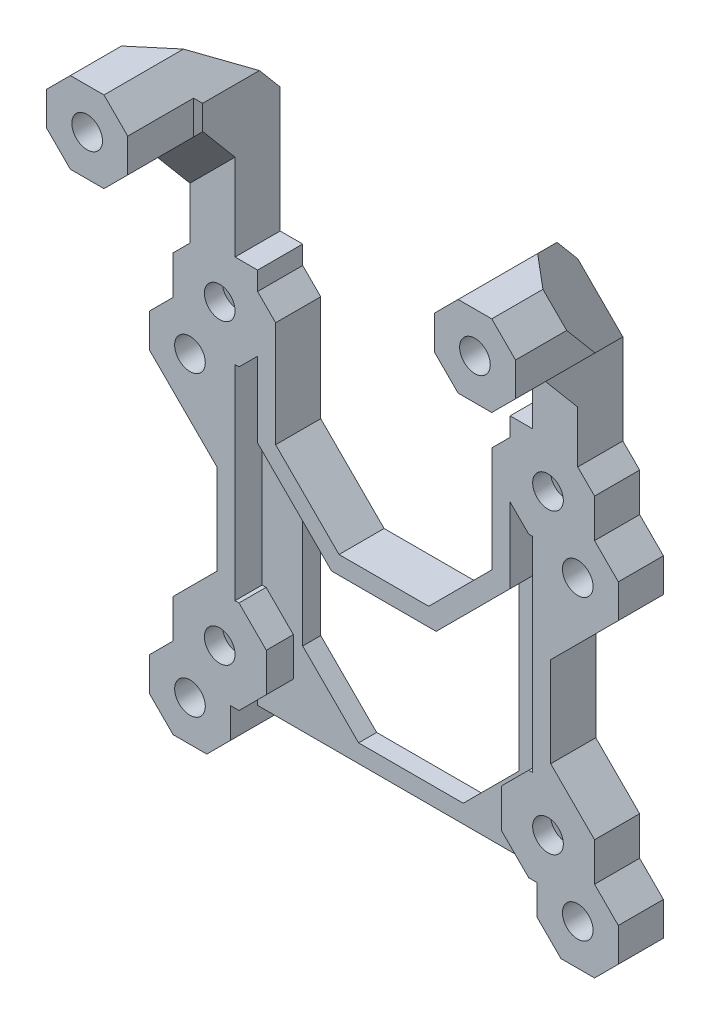
SolidWorks part; units mm, degrees
ref_plane "Front Plane" through (0, 0, 0) normal (0, 0, 1) x (1, 0, 0)
ref_plane "Top Plane" through (0, 0, 0) normal (0, 1, 0) x (1, 0, 0)
ref_plane "Right Plane" through (0, 0, 0) normal (1, 0, 0) x (0, 0, -1)
sketch "Sketch1" plane through (0, 0, 0) normal (0, 0, 1) x (1, 0, 0)
  line L0 (-21.5, 0) -> (21.5, 0) construction
  line L1 (21.5, 0) -> (21.5, 60) construction
  line L2 (21.5, 60) -> (-21.5, 60) construction
  line L3 (-21.5, 60) -> (-21.5, 0) construction
  line L4 (-21.5, 33) -> (21.5, 33) construction
  line L5 (0, 0) -> (0, 60) construction
  line L9 (-5.799, 20) -> (0, 20)
  line L12 (0, 60) -> (0, 76.4523) construction
  line L15 (-16.5, 34.364) -> (-16.5, 60) construction
  line L16 (-20.339, 11.8029) -> (-18.5, 13.6419)
  line L17 (-16.061, 11.8029) -> (-20.339, 11.8029)
  line L18 (-20.339, 11.8029) -> (-23.364, 8.778)
  line L19 (-23.364, 8.778) -> (-23.364, 4.5)
  line L20 (-23.364, 4.5) -> (-20.339, 1.475)
  line L21 (-20.339, 1.475) -> (-16.061, 1.475)
  line L23 (-13.036, 37.5) -> (-13.036, 41.778)
  line L24 (-13.036, 41.778) -> (-16.061, 44.8029)
  line L25 (-16.061, 44.8029) -> (-20.339, 44.8029)
  line L26 (-20.339, 44.8029) -> (-23.364, 41.778)
  line L27 (-23.364, 41.778) -> (-23.364, 37.5)
  line L28 (-23.364, 37.5) -> (-20.339, 34.475)
  line L29 (-20.339, 34.475) -> (-16.061, 34.475)
  line L30 (-16.061, 34.475) -> (-13.036, 37.5)
  line L31 (13.036, 37.5) -> (16.061, 34.475)
  line L32 (16.061, 34.475) -> (20.339, 34.475)
  line L33 (20.339, 34.475) -> (23.364, 37.5)
  line L34 (23.364, 37.5) -> (23.364, 41.778)
  line L35 (23.364, 41.778) -> (20.339, 44.8029)
  line L36 (20.339, 44.8029) -> (16.061, 44.8029)
  line L37 (16.061, 44.8029) -> (13.036, 41.778)
  line L38 (13.036, 41.778) -> (13.036, 37.5)
  line L39 (-14, 0) -> (-14, 51.1419) construction
  line L40 (-16.5, 0) -> (-16.5, 33) construction
  line L41 (-17, 58.136) -> (-17, 61.864)
  line L42 (-17, 61.864) -> (-19.636, 64.5)
  line L43 (-19.636, 64.5) -> (-23.364, 64.5)
  line L44 (-23.364, 64.5) -> (-26, 61.864)
  line L45 (-26, 61.864) -> (-26, 58.136)
  line L46 (-26, 58.136) -> (-23.364, 55.5)
  line L47 (-23.364, 55.5) -> (-19.636, 55.5)
  line L48 (-19.636, 55.5) -> (-17, 58.136)
  line L49 (-23.364, 37.5) -> (-26, 34.864)
  line L50 (-26, 34.864) -> (-26, 31.136)
  line L51 (-26, 31.136) -> (-23.364, 28.5)
  line L52 (-23.364, 28.5) -> (-19.636, 28.5)
  line L53 (-19.636, 28.5) -> (-17, 31.136)
  line L54 (-17, 31.136) -> (-17, 34.864)
  line L55 (-17, 34.864) -> (-19.636, 37.5)
  line L56 (-19.636, 37.5) -> (-23.364, 37.5)
  line L57 (-23.364, 4.5) -> (-26, 1.864)
  line L58 (-26, 1.864) -> (-26, -1.864)
  line L59 (-26, -1.864) -> (-23.364, -4.5)
  line L60 (-23.364, -4.5) -> (-19.636, -4.5)
  line L61 (-19.636, -4.5) -> (-17, -1.864)
  line L62 (-17, -1.864) -> (-17, 1.864)
  line L63 (-17, 1.864) -> (-19.636, 4.5)
  line L64 (-19.636, 4.5) -> (-23.364, 4.5)
  line L65 (23.364, -4.5) -> (26, -1.864)
  line L66 (26, -1.864) -> (26, 1.864)
  line L67 (26, 1.864) -> (23.364, 4.5)
  line L68 (23.364, 4.5) -> (19.636, 4.5)
  line L69 (19.636, 4.5) -> (17, 1.864)
  line L70 (17, 1.864) -> (17, -1.864)
  line L71 (17, -1.864) -> (19.636, -4.5)
  line L72 (19.636, -4.5) -> (23.364, -4.5)
  line L73 (19.636, 28.5) -> (23.364, 28.5)
  line L74 (23.364, 28.5) -> (26, 31.136)
  line L75 (26, 31.136) -> (26, 34.864)
  line L76 (26, 34.864) -> (23.364, 37.5)
  line L77 (23.364, 37.5) -> (19.636, 37.5)
  line L78 (19.636, 37.5) -> (17, 34.864)
  line L79 (17, 34.864) -> (17, 31.136)
  line L80 (17, 31.136) -> (19.636, 28.5)
  line L81 (23.364, 64.5) -> (19.636, 64.5)
  line L82 (19.636, 64.5) -> (17, 61.864)
  line L83 (17, 61.864) -> (17, 58.136)
  line L84 (17, 58.136) -> (19.636, 55.5)
  line L85 (19.636, 55.5) -> (23.364, 55.5)
  line L86 (23.364, 55.5) -> (26, 58.136)
  line L87 (26, 58.136) -> (26, 61.864)
  line L88 (26, 61.864) -> (23.364, 64.5)
  line L89 (-12, 34) -> (-12, 68.1911) construction
  line L90 (12, 34) -> (12, 71.0139) construction
  line L95 (-16.5, 0) -> (-16.5, 34.364)
  line L100 (-4.9706, 22) -> (0, 22)
  line L101 (0, 0) -> (-16.5, 0) construction
  line L103 (-12, 40.7419) -> (-12, 29.0294)
  line L106 (-23.364, 55.5) -> (-21.5, 53.636)
  line L107 (-23.364, 37.5) -> (-21.5, 39.364)
  line L108 (-21.5, 39.364) -> (-21.5, 53.636)
  line L109 (-23.364, 4.5) -> (-18.5, 9.364)
  line L110 (-18.5, 9.364) -> (-18.5, 23.636)
  line L111 (-18.5, 23.636) -> (-23.364, 28.5)
  line L117 (-14, 42.7419) -> (-14, 28.201)
  line L119 (-17, 34.864) -> (-16.5, 34.364)
  line L120 (-19.636, 37.5) -> (-19.5, 37.364)
  line L121 (-19.5, 37.364) -> (-19.5, 55.636)
  line L122 (-19.5, 55.636) -> (-19.636, 55.5)
  line L124 (-19.636, 55.5) -> (-19.5, 55.636)
  line L126 (-16.061, 1.475) -> (-13.036, 4.5)
  line L131 (-4.9706, 22) -> (-12, 29.0294)
  line L132 (-12, 26.201) -> (-12, 8.201)
  line L134 (-12, 26.201) -> (-5.799, 20)
  line L135 (-12, 26.201) -> (-14, 28.201)
  line L136 (-13.036, 4.5) -> (-13.036, 8.778)
  line L137 (-13.036, 8.778) -> (-16.061, 11.8029)
  line L138 (0, 0) -> (-17, 0)
  line L139 (-17, 0) -> (0, 0)
  line L140 (0, 2) -> (-5.799, 2)
  line L141 (-5.799, 2) -> (-12, 8.201)
  line L142 (-13.036, 41.778) -> (-12, 40.7419)
  line L143 (-17, 61.864) -> (-16.5, 61.364)
  line L144 (-16.061, 44.8029) -> (-16.5, 45.2419)
  line L145 (-16.5, 45.2419) -> (-16.5, 61.364)
  line L146 (-16.061, 44.8029) -> (-12, 44.8029)
  line L147 (-16.4968, 42.589) -> (-19.9032, 42.589)
  line L148 (-19.9032, 42.589) -> (-21.6064, 39.639)
  line L149 (-21.6064, 39.639) -> (-19.9032, 36.689)
  line L150 (-19.9032, 36.689) -> (-16.4968, 36.689)
  line L151 (-16.4968, 36.689) -> (-14.7936, 39.639)
  line L152 (-14.7936, 39.639) -> (-16.4968, 42.589)
  line L153 (-16.4968, 9.589) -> (-19.9032, 9.589)
  line L154 (-19.9032, 9.589) -> (-21.6064, 6.639)
  line L155 (-21.6064, 6.639) -> (-19.9032, 3.689)
  line L156 (-19.9032, 3.689) -> (-16.4968, 3.689)
  line L157 (-16.4968, 3.689) -> (-14.7936, 6.639)
  line L158 (-14.7936, 6.639) -> (-16.4968, 9.589)
  line L159 (-12, 44.8029) -> (-12, 40.7419)
  circle A0 centre (-21.5, 60) radius 1.7
  circle A1 centre (-21.5, 33) radius 1.7
  circle A2 centre (-21.5, 0) radius 1.7
  circle A3 centre (21.5, 0) radius 1.7
  circle A4 centre (21.5, 33) radius 1.7
  circle A5 centre (21.5, 60) radius 1.7
  circle A7 centre (-18.2, 6.639) radius 1.7
  circle A8 centre (-18.2, 39.639) radius 1.7
  circle A9 centre (18.2, 39.639) radius 1.7
  circle A10 centre (0, 34) radius 12 construction
  circle A11 centre (0, 56) radius 12 construction
  circle A13 centre (-18.2, 39.639) radius 5.164 construction
  circle A14 centre (18.2, 39.639) radius 5.164 construction
  circle A15 centre (-21.5, 60) radius 4.5 construction
  circle A16 centre (-21.5, 33) radius 4.5 construction
  circle A17 centre (-21.5, 0) radius 4.5 construction
  circle A18 centre (21.5, 0) radius 4.5 construction
  circle A19 centre (21.5, 33) radius 4.5 construction
  circle A20 centre (21.5, 60) radius 4.5 construction
  circle A22 centre (-18.2, 6.639) radius 5.164 construction
  circle A23 centre (-18.2, 39.639) radius 2.95 construction
  circle A24 centre (-18.2, 6.639) radius 2.95 construction
  dimension "D4" = 3.4
  dimension "D5" = 24
  dimension "D7" = 2
  dimension "D8" = 5.9
  dimension "D9" = 9
  dimension "D10" = 9
  dimension "D11" = 9
  dimension "D12" = 9
  dimension "D13" = 9
  dimension "D14" = 9
  dimension "D6" = 2
  dimension "D1" = 43
  dimension "D2" = 33
  dimension "D3" = 27
  dimension "D15" = 2.5
  dimension "D16" = 2
  dimension "D17" = 2
  dimension "D19" = 135
  dimension "D22" = 2
  dimension "D23" = 2
  dimension "D24" = 34
  dimension "D25" = 2
  dimension "D26" = 22
sketch "Sketch5" plane through (0, 0, 0) normal (0, 0, 1) x (1, 0, 0)
  line L0 (16.5, 44.8029) -> (16.5, 45.2419)
  line L1 (16.061, 44.8029) -> (16.5, 44.8029)
  line L12 (0, 0) -> (0, 60) construction
  line L13 (0, 2) -> (-5.799, 2) construction
  line L14 (-5.799, 2) -> (-12, 8.201) construction
  line L15 (-12, 26.201) -> (-12, 8.201) construction
  line L16 (-12, 26.201) -> (-5.799, 20) construction
  line L17 (-5.799, 20) -> (0, 20) construction
  line L18 (-4.9706, 22) -> (0, 22) construction
  line L19 (-4.9706, 22) -> (-12, 29.0294) construction
  line L20 (-12, 40.7419) -> (-12, 29.0294) construction
  line L21 (-13.036, 41.778) -> (-12, 40.7419) construction
  line L22 (-13.036, 41.778) -> (-16.061, 44.8029) construction
  line L24 (-16.5, 45.2419) -> (-16.5, 61.364) construction
  line L25 (-17, 61.864) -> (-16.5, 61.364) construction
  line L26 (-17, 61.864) -> (-19.636, 64.5) construction
  line L27 (-19.636, 64.5) -> (-23.364, 64.5) construction
  line L28 (-23.364, 64.5) -> (-26, 61.864) construction
  line L29 (-26, 61.864) -> (-26, 58.136) construction
  line L30 (-26, 58.136) -> (-23.364, 55.5) construction
  line L31 (-23.364, 55.5) -> (-21.5, 53.636) construction
  line L32 (-21.5, 39.364) -> (-21.5, 53.636) construction
  line L33 (-20.339, 44.8029) -> (-23.364, 41.778) construction
  line L34 (-23.364, 41.778) -> (-23.364, 37.5) construction
  line L35 (-23.364, 37.5) -> (-26, 34.864) construction
  line L36 (-26, 34.864) -> (-26, 31.136) construction
  line L37 (-26, 31.136) -> (-23.364, 28.5) construction
  line L38 (-18.5, 23.636) -> (-23.364, 28.5) construction
  line L39 (-18.5, 9.364) -> (-18.5, 23.636) construction
  line L40 (-20.339, 11.8029) -> (-18.5, 13.6419) construction
  line L41 (-20.339, 11.8029) -> (-23.364, 8.778) construction
  line L42 (-23.364, 8.778) -> (-23.364, 4.5) construction
  line L43 (-23.364, 4.5) -> (-26, 1.864) construction
  line L44 (-26, 1.864) -> (-26, -1.864) construction
  line L45 (-26, -1.864) -> (-23.364, -4.5) construction
  line L46 (-23.364, -4.5) -> (-19.636, -4.5) construction
  line L47 (-19.636, -4.5) -> (-17, -1.864) construction
  line L48 (-17, -1.864) -> (-17, 1.864) construction
  line L49 (0, 0) -> (-17, 0) construction
  line L50 (0, 0) -> (0, 60) construction
  line L51 (5.799, 2) -> (-5.799, 2)
  line L52 (-5.799, 2) -> (-12, 8.201)
  line L53 (-12, 26.201) -> (-12, 8.201)
  line L54 (-12, 26.201) -> (-5.799, 20)
  line L55 (-5.799, 20) -> (5.799, 20)
  line L56 (-4.9706, 22) -> (4.9706, 22)
  line L57 (-4.9706, 22) -> (-12, 29.0294)
  line L58 (-12, 40.7419) -> (-12, 29.0294)
  line L59 (-13.036, 41.778) -> (-12, 40.7419)
  line L60 (-13.036, 41.778) -> (-14, 42.7419)
  line L62 (-16.5, 60) -> (-16.5, 61.364)
  line L63 (-17, 61.864) -> (-16.5, 61.364)
  line L64 (-17, 61.864) -> (-19.636, 64.5)
  line L65 (-19.636, 64.5) -> (-23.364, 64.5)
  line L66 (-23.364, 64.5) -> (-26, 61.864)
  line L67 (-26, 61.864) -> (-26, 58.136)
  line L68 (-26, 58.136) -> (-23.364, 55.5)
  line L69 (-23.364, 55.5) -> (-21.5, 53.636)
  line L70 (-21.5, 43.6419) -> (-21.5, 53.636)
  line L71 (-21.5, 43.6419) -> (-23.364, 41.778)
  line L72 (-23.364, 41.778) -> (-23.364, 37.5)
  line L73 (-23.364, 37.5) -> (-26, 34.864)
  line L74 (-26, 34.864) -> (-26, 31.136)
  line L75 (-26, 31.136) -> (-23.364, 28.5)
  line L76 (-18.5, 23.636) -> (-23.364, 28.5)
  line L77 (-18.5, 13.6419) -> (-18.5, 23.636)
  line L78 (-20.339, 11.8029) -> (-18.5, 13.6419)
  line L79 (-20.339, 11.8029) -> (-23.364, 8.778)
  line L80 (-23.364, 8.778) -> (-23.364, 4.5)
  line L81 (-23.364, 4.5) -> (-26, 1.864)
  line L82 (-26, 1.864) -> (-26, -1.864)
  line L83 (-26, -1.864) -> (-23.364, -4.5)
  line L84 (-23.364, -4.5) -> (-19.636, -4.5)
  line L85 (-19.636, -4.5) -> (-17, -1.864)
  line L86 (-17, -1.864) -> (-17, 0)
  line L87 (17, 0) -> (-17, 0)
  line L88 (17, -1.864) -> (17, 0)
  line L89 (19.636, -4.5) -> (17, -1.864)
  line L90 (23.364, -4.5) -> (19.636, -4.5)
  line L91 (26, -1.864) -> (23.364, -4.5)
  line L92 (26, 1.864) -> (26, -1.864)
  line L93 (23.364, 4.5) -> (26, 1.864)
  line L94 (23.364, 8.778) -> (23.364, 4.5)
  line L95 (20.339, 11.8029) -> (23.364, 8.778)
  line L96 (20.339, 11.8029) -> (18.5, 13.6419)
  line L97 (18.5, 13.6419) -> (18.5, 23.636)
  line L98 (18.5, 23.636) -> (23.364, 28.5)
  line L99 (26, 31.136) -> (23.364, 28.5)
  line L100 (26, 34.864) -> (26, 31.136)
  line L101 (23.364, 37.5) -> (26, 34.864)
  line L139 (23.364, 41.778) -> (23.364, 37.5)
  line L140 (21.5, 43.6419) -> (23.364, 41.778)
  line L141 (21.5, 43.6419) -> (21.5, 53.636)
  line L142 (23.364, 55.5) -> (21.5, 53.636)
  line L143 (26, 58.136) -> (23.364, 55.5)
  line L144 (26, 61.864) -> (26, 58.136)
  line L145 (23.364, 64.5) -> (26, 61.864)
  line L146 (19.636, 64.5) -> (23.364, 64.5)
  line L147 (17, 61.864) -> (19.636, 64.5)
  line L148 (17, 61.864) -> (16.5, 61.364)
  line L149 (16.5, 45.2419) -> (16.5, 61.364)
  line L151 (13.036, 41.778) -> (14, 42.7419)
  line L152 (13.036, 41.778) -> (12, 40.7419)
  line L153 (12, 40.7419) -> (12, 29.0294)
  line L154 (4.9706, 22) -> (12, 29.0294)
  line L155 (12, 26.201) -> (5.799, 20)
  line L156 (12, 26.201) -> (12, 8.201)
  line L157 (5.799, 2) -> (12, 8.201)
  line L158 (-16.061, 44.8029) -> (-12, 44.8029) construction
  line L159 (-14, 0) -> (-14, 51.1419) construction
  line L160 (-16.061, 44.8029) -> (-14, 44.8029)
  line L161 (-14, 42.7419) -> (-14, 44.8029)
  line L162 (14, 42.7419) -> (14, 44.8029)
  line L163 (16.061, 44.8029) -> (14, 44.8029)
  line L164 (-16.061, 44.8029) -> (-20.339, 44.8029) construction
  line L165 (-16.5, 34.364) -> (-16.5, 60) construction
  line L166 (-16.061, 44.8029) -> (-16.5, 44.8029)
  line L167 (-16.5, 44.8029) -> (-16.5, 60)
  circle A0 centre (-18.2, 6.639) radius 1.7 construction
  circle A1 centre (-18.2, 39.639) radius 1.7 construction
  circle A2 centre (-18.2, 6.639) radius 1.7
  circle A3 centre (-18.2, 39.639) radius 1.7
  circle A4 centre (18.2, 39.639) radius 1.7
  circle A5 centre (18.2, 6.639) radius 1.7
extrude "Boss-Extrude1" add sketch "Sketch5" along normal blind 2
sketch "Sketch9" plane through (0, 0, 2) normal (0, 0, 1) x (1, 0, 0)
  line L0 (0, 0) -> (0, 60) construction
  line L1 (-19.636, -4.5) -> (-17, -1.864) construction
  line L3 (-20.339, 1.475) -> (-16.061, 1.475) construction
  line L4 (-16.061, 1.475) -> (-13.036, 4.5) construction
  line L5 (-13.036, 4.5) -> (-13.036, 8.778) construction
  line L6 (-13.036, 8.778) -> (-16.061, 11.8029) construction
  line L7 (-16.061, 11.8029) -> (-20.339, 11.8029) construction
  line L8 (-20.339, 34.475) -> (-16.061, 34.475) construction
  line L10 (-16.061, 34.475) -> (-13.036, 37.5) construction
  line L13 (-12, 26.201) -> (-14, 28.201) construction
  line L14 (-4.9706, 22) -> (-12, 29.0294) construction
  line L15 (-12, 26.201) -> (-5.799, 20) construction
  line L16 (-5.799, 20) -> (0, 20) construction
  line L17 (-4.9706, 22) -> (0, 22) construction
  line L18 (-12, 40.7419) -> (-12, 29.0294) construction
  line L19 (-13.036, 41.778) -> (-12, 40.7419) construction
  line L22 (-16.5, 45.2419) -> (-16.5, 61.364) construction
  line L23 (-17, 61.864) -> (-19.636, 64.5) construction
  line L24 (-19.636, 64.5) -> (-23.364, 64.5) construction
  line L25 (-23.364, 64.5) -> (-26, 61.864) construction
  line L26 (-26, 61.864) -> (-26, 58.136) construction
  line L27 (-26, 58.136) -> (-23.364, 55.5) construction
  line L28 (-23.364, 55.5) -> (-21.5, 53.636) construction
  line L29 (-21.5, 39.364) -> (-21.5, 53.636) construction
  line L30 (-20.339, 44.8029) -> (-23.364, 41.778) construction
  line L31 (-23.364, 41.778) -> (-23.364, 37.5) construction
  line L32 (-23.364, 37.5) -> (-26, 34.864) construction
  line L33 (-26, 34.864) -> (-26, 31.136) construction
  line L34 (-26, 31.136) -> (-23.364, 28.5) construction
  line L35 (0, 0) -> (0, 60) construction
  line L36 (-19.636, -4.5) -> (-17, -1.864)
  line L37 (-16.5, 11.8029) -> (-16.5, 34.364)
  line L38 (17, 1.475) -> (16.061, 1.475)
  line L39 (-16.061, 1.475) -> (-13.036, 4.5)
  line L40 (-13.036, 4.5) -> (-13.036, 8.778)
  line L41 (-13.036, 8.778) -> (-16.061, 11.8029)
  line L42 (-16.061, 11.8029) -> (-16.5, 11.8029)
  line L43 (-16.5, 34.475) -> (-16.061, 34.475)
  line L44 (-16.5, 34.364) -> (-16.5, 60) construction
  line L45 (-16.061, 34.475) -> (-14, 36.536)
  line L46 (-18.5, 23.636) -> (-23.364, 28.5) construction
  line L47 (-14, 28.201) -> (-14, 36.536)
  line L48 (-12, 26.201) -> (-14, 28.201)
  line L49 (-4.9706, 22) -> (-12, 29.0294)
  line L50 (-12, 26.201) -> (-5.799, 20)
  line L51 (-5.799, 20) -> (5.799, 20)
  line L52 (-4.9706, 22) -> (4.9706, 22)
  line L53 (-12, 40.7419) -> (-12, 29.0294)
  line L54 (-13.036, 41.778) -> (-12, 40.7419)
  line L55 (-13.036, 41.778) -> (-16.061, 44.8029) construction
  line L57 (-16.5, 60) -> (-16.5, 61.364)
  line L58 (-17, 61.864) -> (-19.636, 64.5)
  line L59 (-19.636, 64.5) -> (-23.364, 64.5)
  line L60 (-23.364, 64.5) -> (-26, 61.864)
  line L61 (-26, 61.864) -> (-26, 58.136)
  line L62 (-26, 58.136) -> (-23.364, 55.5)
  line L63 (-23.364, 55.5) -> (-21.5, 53.636)
  line L64 (-21.5, 43.6419) -> (-21.5, 53.636)
  line L65 (-21.5, 43.6419) -> (-23.364, 41.778)
  line L66 (-23.364, 41.778) -> (-23.364, 37.5)
  line L67 (-23.364, 37.5) -> (-26, 34.864)
  line L68 (-26, 34.864) -> (-26, 31.136)
  line L69 (-26, 31.136) -> (-23.364, 28.5)
  line L70 (-18.5, 9.364) -> (-18.5, 23.636) construction
  line L71 (-20.339, 11.8029) -> (-18.5, 13.6419) construction
  line L72 (-20.339, 11.8029) -> (-23.364, 8.778) construction
  line L74 (-23.364, 8.778) -> (-23.364, 4.5) construction
  line L75 (-23.364, 4.5) -> (-26, 1.864) construction
  line L96 (-26, 1.864) -> (-26, -1.864) construction
  line L116 (-26, -1.864) -> (-23.364, -4.5) construction
  line L117 (-18.5, 13.6419) -> (-18.5, 23.636)
  line L118 (-20.339, 11.8029) -> (-18.5, 13.6419)
  line L119 (-20.339, 11.8029) -> (-23.364, 8.778)
  line L120 (-23.364, 8.778) -> (-23.364, 4.5)
  line L121 (-23.364, 4.5) -> (-26, 1.864)
  line L122 (-26, 1.864) -> (-26, -1.864)
  line L123 (-26, -1.864) -> (-23.364, -4.5)
  line L124 (-16.061, 44.8029) -> (-20.339, 44.8029) construction
  line L126 (-17, -1.864) -> (-17, 1.864) construction
  line L127 (-23.364, -4.5) -> (-19.636, -4.5) construction
  line L128 (-18.5, 23.636) -> (-23.364, 28.5)
  line L129 (-17, -1.864) -> (-17, 1.475)
  line L130 (-23.364, -4.5) -> (-19.636, -4.5)
  line L131 (-17, 1.475) -> (-16.061, 1.475)
  line L132 (-17, 61.864) -> (-16.5, 61.364) construction
  line L133 (-17, 61.864) -> (-16.5, 61.364)
  line L134 (17, 61.864) -> (16.5, 61.364)
  line L135 (-13.036, 41.778) -> (-14, 42.7419)
  line L136 (23.364, -4.5) -> (19.636, -4.5)
  line L137 (17, -1.864) -> (17, 1.475)
  line L138 (18.5, 23.636) -> (23.364, 28.5)
  line L139 (16.5, 44.8029) -> (16.5, 45.2419)
  line L140 (26, -1.864) -> (23.364, -4.5)
  line L141 (26, 1.864) -> (26, -1.864)
  line L142 (23.364, 4.5) -> (26, 1.864)
  line L143 (23.364, 8.778) -> (23.364, 4.5)
  line L144 (20.339, 11.8029) -> (23.364, 8.778)
  line L145 (20.339, 11.8029) -> (18.5, 13.6419)
  line L146 (18.5, 13.6419) -> (18.5, 23.636)
  line L147 (26, 31.136) -> (23.364, 28.5)
  line L148 (26, 34.864) -> (26, 31.136)
  line L149 (23.364, 37.5) -> (26, 34.864)
  line L150 (23.364, 41.778) -> (23.364, 37.5)
  line L151 (21.5, 43.6419) -> (23.364, 41.778)
  line L152 (21.5, 43.6419) -> (21.5, 53.636)
  line L153 (23.364, 55.5) -> (21.5, 53.636)
  line L154 (26, 58.136) -> (23.364, 55.5)
  line L155 (26, 61.864) -> (26, 58.136)
  line L156 (23.364, 64.5) -> (26, 61.864)
  line L157 (19.636, 64.5) -> (23.364, 64.5)
  line L158 (17, 61.864) -> (19.636, 64.5)
  line L159 (16.5, 45.2419) -> (16.5, 61.364)
  line L160 (13.036, 41.778) -> (14, 42.7419)
  line L161 (13.036, 41.778) -> (12, 40.7419)
  line L172 (12, 40.7419) -> (12, 29.0294)
  line L173 (12, 26.201) -> (5.799, 20)
  line L174 (4.9706, 22) -> (12, 29.0294)
  line L175 (12, 26.201) -> (14, 28.201)
  line L176 (14, 36.536) -> (14, 28.201)
  line L177 (16.061, 34.475) -> (14, 36.536)
  line L178 (16.5, 34.364) -> (16.5, 34.475)
  line L179 (16.5, 34.475) -> (16.061, 34.475)
  line L180 (16.061, 11.8029) -> (16.5, 11.8029)
  line L181 (13.036, 8.778) -> (16.061, 11.8029)
  line L182 (13.036, 4.5) -> (13.036, 8.778)
  line L183 (16.061, 1.475) -> (13.036, 4.5)
  line L184 (-16.061, 44.8029) -> (-12, 44.8029) construction
  line L185 (16.5, 11.8029) -> (16.5, 34.364)
  line L186 (19.636, -4.5) -> (17, -1.864)
  line L188 (-16.5, 34.364) -> (-16.5, 34.475)
  line L189 (-16.5, 44.8029) -> (-16.5, 60)
  line L190 (-14, 42.7419) -> (-14, 44.8029)
  line L191 (16.061, 44.8029) -> (14, 44.8029)
  line L192 (14, 42.7419) -> (14, 44.8029)
  line L193 (-16.061, 44.8029) -> (-16.5, 44.8029)
  line L194 (-16.061, 44.8029) -> (-14, 44.8029)
  line L196 (16.061, 44.8029) -> (16.5, 44.8029)
  circle A0 centre (-21.5, 33) radius 1.7 construction
  circle A1 centre (-18.2, 39.639) radius 1.7 construction
  circle A3 centre (-21.5, 0) radius 1.7 construction
  circle A4 centre (-18.2, 6.639) radius 1.7 construction
  circle A8 centre (-21.5, 33) radius 1.7
  circle A9 centre (-18.2, 39.639) radius 1.7
  circle A10 centre (-21.5, 0) radius 1.7
  circle A11 centre (-18.2, 6.639) radius 1.7
  circle A12 centre (18.2, 6.639) radius 1.7
  circle A13 centre (21.5, 0) radius 1.7
  circle A14 centre (18.2, 39.639) radius 1.7
  circle A15 centre (21.5, 33) radius 1.7
extrude "Boss-Extrude3" add sketch "Sketch9" along normal blind 3
sketch "Sketch10" plane through (0, 0, 5) normal (0, 0, 1) x (1, 0, 0)
  line L0 (0, 0) -> (0, 60) construction
  line L2 (-17, 61.864) -> (-19.636, 64.5) construction
  line L3 (-19.636, 64.5) -> (-23.364, 64.5) construction
  line L4 (-23.364, 64.5) -> (-26, 61.864) construction
  line L5 (-26, 61.864) -> (-26, 58.136) construction
  line L6 (-26, 58.136) -> (-23.364, 55.5) construction
  line L8 (-19.636, 55.5) -> (-17, 58.136) construction
  line L9 (0, 0) -> (0, 60) construction
  line L10 (17, 58.136) -> (16.5, 58.636)
  line L11 (-17, 61.864) -> (-19.636, 64.5)
  line L12 (-19.636, 64.5) -> (-23.364, 64.5)
  line L13 (-23.364, 64.5) -> (-26, 61.864)
  line L14 (-26, 61.864) -> (-26, 58.136)
  line L15 (-26, 58.136) -> (-23.364, 55.5)
  line L16 (19.636, 55.5) -> (21.5, 53.636)
  line L17 (-19.636, 55.5) -> (-17, 58.136)
  line L18 (23.364, 55.5) -> (21.5, 53.636)
  line L19 (16.5, 58.636) -> (16.5, 61.364)
  line L20 (17, 61.864) -> (16.5, 61.364)
  line L22 (19.636, 55.5) -> (17, 58.136)
  line L23 (26, 58.136) -> (23.364, 55.5)
  line L24 (26, 61.864) -> (26, 58.136)
  line L25 (23.364, 64.5) -> (26, 61.864)
  line L26 (19.636, 64.5) -> (23.364, 64.5)
  line L27 (-17, 61.864) -> (-16.5, 61.364) construction
  line L28 (-16.5, 45.2419) -> (-16.5, 61.364) construction
  line L29 (-23.364, 55.5) -> (-21.5, 53.636) construction
  line L44 (-17, 61.864) -> (-16.5, 61.364)
  line L49 (-16.5, 58.636) -> (-16.5, 61.364)
  line L50 (-23.364, 55.5) -> (-21.5, 53.636)
  line L51 (-19.636, 55.5) -> (-21.5, 53.636)
  line L52 (-17, 58.136) -> (-16.5, 58.636)
  line L53 (17, 61.864) -> (19.636, 64.5)
extrude "Boss-Extrude4" add sketch "Sketch10" along normal blind 3.6
sketch "Sketch20" plane through (0, 0, 8.6) normal (0, 0, 1) x (1, 0, 0)
  line L0 (0, 60) -> (0, 76.4523) construction
  line L1 (-17, 58.136) -> (-17, 61.864) construction
  line L2 (-19.636, 55.5) -> (-17, 58.136) construction
  line L3 (-23.364, 55.5) -> (-19.636, 55.5) construction
  line L4 (-26, 58.136) -> (-23.364, 55.5) construction
  line L5 (-26, 61.864) -> (-26, 58.136) construction
  line L6 (-23.364, 64.5) -> (-26, 61.864) construction
  line L7 (-19.636, 64.5) -> (-23.364, 64.5) construction
  line L8 (-17, 61.864) -> (-19.636, 64.5) construction
  line L9 (0, 60) -> (0, 76.4523) construction
  line L10 (-17, 58.136) -> (-17, 61.864)
  line L11 (-19.636, 55.5) -> (-17, 58.136)
  line L12 (-23.364, 55.5) -> (-19.636, 55.5)
  line L13 (-26, 58.136) -> (-23.364, 55.5)
  line L14 (-26, 61.864) -> (-26, 58.136)
  line L15 (-23.364, 64.5) -> (-26, 61.864)
  line L16 (-19.636, 64.5) -> (-23.364, 64.5)
  line L17 (-17, 61.864) -> (-19.636, 64.5)
  line L18 (17, 61.864) -> (19.636, 64.5)
  line L19 (19.636, 64.5) -> (23.364, 64.5)
  line L20 (23.364, 64.5) -> (26, 61.864)
  line L21 (26, 61.864) -> (26, 58.136)
  line L22 (26, 58.136) -> (23.364, 55.5)
  line L23 (23.364, 55.5) -> (19.636, 55.5)
  line L24 (19.636, 55.5) -> (17, 58.136)
  line L25 (17, 58.136) -> (17, 61.864)
extrude "Boss-Extrude5" add sketch "Sketch20" along normal blind 7.8
ref_plane "Plane1" through (19.25, 19.25, 0) normal (0.7071, 0.7071, 0) x (0, 0, -1)
ref_plane "Plane2" through (-19.25, 19.25, 0) normal (-0.7071, 0.7071, 0) x (0.7071, 0.7071, 0)
sketch "Sketch15" plane through (19.25, 19.25, 0) normal (0.7071, 0.7071, 0) x (0, 0, -1)
  line L0 (0, 53.1292) -> (-15.3209, 65.985)
  line L1 (-15.3209, 65.985) -> (-8.893, 73.6454)
  line L2 (-8.893, 73.6454) -> (6.4279, 60.7896)
  line L3 (6.4279, 60.7896) -> (0, 53.1292)
  line L5 (0, 62.1292) -> (0, 53.1292) construction
  dimension "D1" = 20
  dimension "D2" = 10
  dimension "D3" = 50
extrude "Top Angle 1" cut sketch "Sketch15" against normal mid plane 50
sketch "Sketch16" plane through (-19.25, 19.25, 0) normal (-0.7071, 0.7071, 0) x (0.7071, 0.7071, 0)
  line L0 (53.1292, 0) -> (65.985, -15.3209)
  line L1 (65.985, -15.3209) -> (73.6454, -8.893)
  line L2 (73.6454, -8.893) -> (60.7896, 6.4279)
  line L3 (60.7896, 6.4279) -> (53.1292, 0)
  line L7 (55.7652, 0) -> (59.4932, 0) construction
  dimension "D1" = 50
  dimension "D2" = 20
  dimension "D3" = 10
extrude "Top Angle 2" cut sketch "Sketch16" against normal mid plane 50
chamfer "Chamfer1" distance 3 angle 50 2 edges at (-19, 56.136, 5) (19, 56.136, 5)
chamfer "Chamfer2" distance 1.8 angle 50 2 edges
sketch "Sketch18" plane through (0, 0, 0) normal (0, 0, -1) x (-1, 0, 0)
  line L1 (16.4968, 42.589) -> (19.9032, 42.589) construction
  line L2 (19.9032, 42.589) -> (21.6064, 39.639) construction
  line L3 (21.6064, 39.639) -> (19.9032, 36.689) construction
  line L4 (19.9032, 36.689) -> (16.4968, 36.689) construction
  line L5 (16.4968, 36.689) -> (14.7936, 39.639) construction
  line L6 (14.7936, 39.639) -> (16.4968, 42.589) construction
  line L7 (19.9032, 9.589) -> (21.6064, 6.639) construction
  line L8 (16.4968, 9.589) -> (19.9032, 9.589) construction
  line L9 (14.7936, 6.639) -> (16.4968, 9.589) construction
  line L10 (16.4968, 3.689) -> (14.7936, 6.639) construction
  line L11 (19.9032, 3.689) -> (16.4968, 3.689) construction
  line L12 (21.6064, 6.639) -> (19.9032, 3.689) construction
  line L13 (0, 0) -> (0, 60) construction
  line L14 (16.4968, 42.589) -> (19.9032, 42.589)
  line L15 (19.9032, 42.589) -> (21.6064, 39.639)
  line L16 (21.6064, 39.639) -> (19.9032, 36.689)
  line L17 (19.9032, 36.689) -> (16.4968, 36.689)
  line L18 (16.4968, 36.689) -> (14.7936, 39.639)
  line L19 (14.7936, 39.639) -> (16.4968, 42.589)
  line L20 (19.9032, 9.589) -> (21.6064, 6.639)
  line L21 (16.4968, 9.589) -> (19.9032, 9.589)
  line L22 (14.7936, 6.639) -> (16.4968, 9.589)
  line L23 (16.4968, 3.689) -> (14.7936, 6.639)
  line L24 (19.9032, 3.689) -> (16.4968, 3.689)
  line L25 (21.6064, 6.639) -> (19.9032, 3.689)
  line L26 (0, 0) -> (0, 60) construction
  line L27 (-21.6064, 6.639) -> (-19.9032, 3.689)
  line L28 (-19.9032, 3.689) -> (-16.4968, 3.689)
  line L29 (-16.4968, 3.689) -> (-14.7936, 6.639)
  line L30 (-14.7936, 6.639) -> (-16.4968, 9.589)
  line L31 (-16.4968, 9.589) -> (-19.9032, 9.589)
  line L32 (-19.9032, 9.589) -> (-21.6064, 6.639)
  line L33 (-14.7936, 39.639) -> (-16.4968, 42.589)
  line L34 (-16.4968, 36.689) -> (-14.7936, 39.639)
  line L35 (-19.9032, 36.689) -> (-16.4968, 36.689)
  line L36 (-21.6064, 39.639) -> (-19.9032, 36.689)
  line L37 (-19.9032, 42.589) -> (-21.6064, 39.639)
  line L38 (-16.4968, 42.589) -> (-19.9032, 42.589)
sketch "Sketch19" plane through (0, 0, 16.4) normal (0, 0, 1) x (1, 0, 0)
  circle A0 centre (-21.5, 60) radius 1.7 construction
  circle A1 centre (21.5, 60) radius 1.7 construction
  circle A2 centre (-21.5, 60) radius 1.7
  circle A3 centre (21.5, 60) radius 1.7
extrude "Cut-Extrude1" cut sketch "Sketch19" against normal blind 3.75
extrude "M3 Head Holes" cut sketch "Sketch18" against normal blind 3
chamfer "Chamfer3" distance 0.5 angle 45 2 edges
ref_plane "Print Support Plane" through (0, 0, 3) normal (0, 0, -1) x (-1, 0, 0)
sketch "Sketch17" plane through (0, 0, 3) normal (0, 0, -1) x (-1, 0, 0)
  line L0 (0, 0) -> (0, 60) construction
  line L1 (0, 0) -> (0, 60) construction
  circle A4 centre (18.2, 39.639) radius 1.7 construction
  circle A5 centre (18.2, 6.639) radius 1.7 construction
  circle A6 centre (-18.2, 6.639) radius 1.7 construction
  circle A7 centre (-18.2, 39.639) radius 1.7 construction
  circle A8 centre (18.2, 39.639) radius 1.7
  circle A9 centre (18.2, 6.639) radius 1.7
  circle A10 centre (-18.2, 6.639) radius 1.7
  circle A11 centre (-18.2, 39.639) radius 1.7
extrude "Support Material" [suppressed] add sketch "Sketch17" against normal blind 0.3
